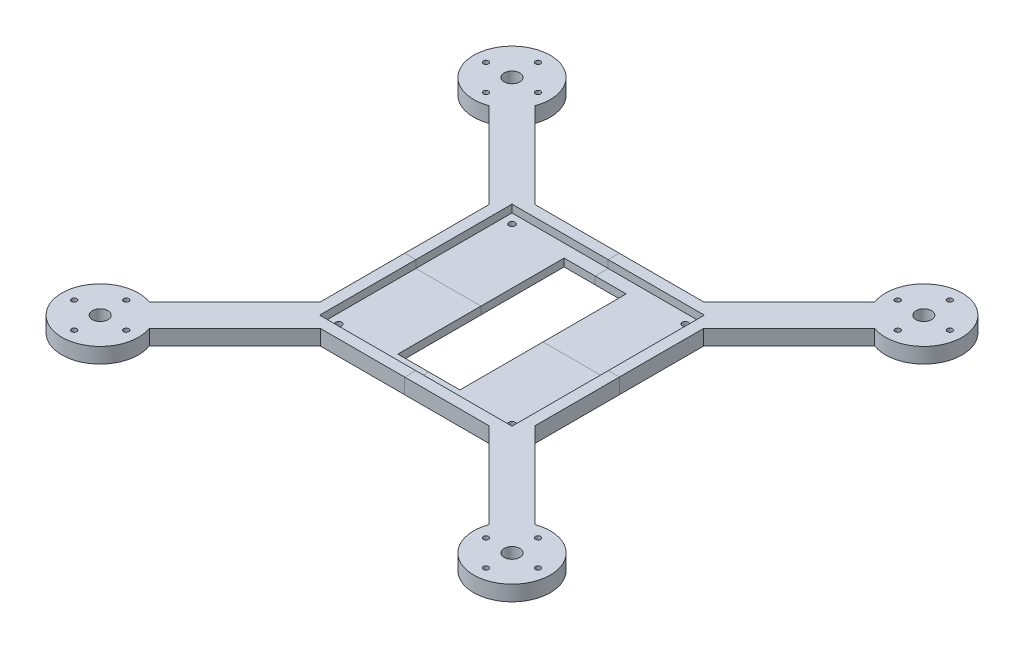
SolidWorks part; units mm, degrees
ref_plane "정면" through (0, 0, 0) normal (0, 0, 1) x (1, 0, 0)
ref_plane "윗면" through (0, 0, 0) normal (0, 1, 0) x (1, 0, 0)
ref_plane "우측면" through (0, 0, 0) normal (1, 0, 0) x (0, 0, -1)
sketch "스케치1" plane through (0, 0, 0) normal (0, 1, 0) x (1, 0, 0)
  line L0 (55, 70) -> (110.8425, 125.8425)
  line L1 (-55, 70) -> (55, 70)
  line L2 (-70, 55) -> (-70, -55)
  line L3 (-55, -70) -> (55, -70)
  line L4 (70, 55) -> (70, -55)
  line L5 (-60.2755, 60.2755) -> (60.2245, -60.2245) construction
  line L6 (-77.3477, -77.3477) -> (43.1523, 43.1523) construction
  line L7 (-20.25, 54.25) -> (20.25, 54.25)
  line L8 (-20.25, 54.25) -> (-20.25, -54.25)
  line L9 (-20.25, -54.25) -> (20.25, -54.25)
  line L10 (20.25, 54.25) -> (20.25, -54.25)
  line L11 (-20.25, 54.25) -> (20.25, -54.25) construction
  line L12 (-20.25, -54.25) -> (20.25, 54.25) construction
  line L13 (70, 55) -> (125.8425, 110.8425)
  line L14 (109.3503, 134.3503) -> (159.3503, 134.3503) construction
  line L15 (134.3503, 159.3503) -> (134.3503, 109.3503) construction
  line L16 (152.028, 116.6726) -> (116.6726, 152.028) construction
  line L17 (70, -55) -> (125.8425, -110.8425)
  line L18 (55, -70) -> (110.8425, -125.8425)
  line L19 (134.3503, -109.3503) -> (134.3503, -159.3503) construction
  line L20 (159.3503, -134.3503) -> (109.3503, -134.3503) construction
  line L21 (116.6726, -152.028) -> (152.028, -116.6726) construction
  line L22 (-55, -70) -> (-110.8425, -125.8425)
  line L23 (-70, -55) -> (-125.8425, -110.8425)
  line L24 (-109.3503, -134.3503) -> (-159.3503, -134.3503) construction
  line L25 (-134.3503, -159.3503) -> (-134.3503, -109.3503) construction
  line L26 (-152.028, -116.6726) -> (-116.6726, -152.028) construction
  line L27 (-70, 55) -> (-125.8425, 110.8425)
  line L28 (-55, 70) -> (-110.8425, 125.8425)
  line L29 (-134.3503, 109.3503) -> (-134.3503, 159.3503) construction
  line L30 (-159.3503, 134.3503) -> (-109.3503, 134.3503) construction
  line L31 (-116.6726, 152.028) -> (-152.028, 116.6726) construction
  line L32 (55, 70) -> (70, 70) construction
  line L33 (70, 70) -> (70, 55) construction
  line L34 (55, -70) -> (70, -70) construction
  line L35 (70, -55) -> (70, -70) construction
  line L36 (-70, -70) -> (-55, -70) construction
  line L37 (-70, -55) -> (-70, -70) construction
  line L38 (-70, 70) -> (-70, 55) construction
  line L39 (-70, 70) -> (-55, 70) construction
  line L45 (-56.5, 56.5) -> (56.5, -56.5) construction
  line L46 (-56.5, -56.5) -> (56.5, 56.5) construction
  circle A0 centre (-56.5, -56.5) radius 2
  circle A1 centre (56.5, -56.5) radius 2
  circle A2 centre (56.5, 56.5) radius 2
  circle A3 centre (-56.5, 56.5) radius 2
  arc A4 (125.8425, 110.8425) -> (110.8425, 125.8425) centre (134.3503, 134.3503) ccw
  arc A5 (110.8425, 125.8425) -> (116.6726, 116.6726) centre (134.3503, 134.3503) ccw construction
  arc A6 (116.6726, 116.6726) -> (125.8425, 110.8425) centre (134.3503, 134.3503) ccw construction
  circle A11 centre (134.3503, 117.3503) radius 1.7
  circle A12 centre (117.3503, 134.3503) radius 1.7
  circle A13 centre (151.3503, 134.3503) radius 1.7
  circle A14 centre (134.3503, 151.3503) radius 1.7
  circle A15 centre (134.3503, 134.3503) radius 5.1
  arc A16 (110.8425, -125.8425) -> (125.8425, -110.8425) centre (134.3503, -134.3503) ccw
  circle A17 centre (117.3503, -134.3503) radius 1.7
  circle A18 centre (134.3503, -117.3503) radius 1.7
  circle A19 centre (134.3503, -151.3503) radius 1.7
  circle A20 centre (151.3503, -134.3503) radius 1.7
  circle A21 centre (134.3503, -134.3503) radius 5.1
  arc A22 (125.8425, -110.8425) -> (116.6726, -116.6726) centre (134.3503, -134.3503) ccw construction
  arc A23 (116.6726, -116.6726) -> (110.8425, -125.8425) centre (134.3503, -134.3503) ccw construction
  arc A24 (-125.8425, -110.8425) -> (-110.8425, -125.8425) centre (-134.3503, -134.3503) ccw
  circle A25 centre (-134.3503, -117.3503) radius 1.7
  circle A26 centre (-117.3503, -134.3503) radius 1.7
  circle A27 centre (-151.3503, -134.3503) radius 1.7
  circle A28 centre (-134.3503, -151.3503) radius 1.7
  circle A29 centre (-134.3503, -134.3503) radius 5.1
  arc A30 (-110.8425, -125.8425) -> (-116.6726, -116.6726) centre (-134.3503, -134.3503) ccw construction
  arc A31 (-116.6726, -116.6726) -> (-125.8425, -110.8425) centre (-134.3503, -134.3503) ccw construction
  arc A32 (-110.8425, 125.8425) -> (-125.8425, 110.8425) centre (-134.3503, 134.3503) ccw
  circle A33 centre (-117.3503, 134.3503) radius 1.7
  circle A34 centre (-134.3503, 117.3503) radius 1.7
  circle A35 centre (-134.3503, 151.3503) radius 1.7
  circle A36 centre (-151.3503, 134.3503) radius 1.7
  circle A37 centre (-134.3503, 134.3503) radius 5.1
  arc A38 (-125.8425, 110.8425) -> (-116.6726, 116.6726) centre (-134.3503, 134.3503) ccw construction
  arc A39 (-116.6726, 116.6726) -> (-110.8425, 125.8425) centre (-134.3503, 134.3503) ccw construction
  point P0 (0, 0)
  point P6 (0, 0)
  point P28 (0, 54.25)
  point P32 (134.3503, 134.3503)
  point P38 (134.3503, 134.3503)
  point P48 (0, 0)
  point P57 (134.3503, -134.3503)
  point P63 (134.3503, -134.3503)
  point P80 (-134.3503, -134.3503)
  point P86 (-134.3503, -134.3503)
  point P103 (-134.3503, 134.3503)
  point P109 (-134.3503, 134.3503)
  dimension "D5" = 4
  dimension "D13" = 50
  dimension "D14" = 3.4
  dimension "D15" = 17
  dimension "D16" = 34
  dimension "D19" = 10.2
  dimension "D1" = 140
  dimension "D2" = 140
  dimension "D3" = 108.5
  dimension "D4" = 40.5
  dimension "D6" = 56.5
  dimension "D10" = 15
  dimension "D11" = 15
  dimension "D12" = 190
  dimension "D17" = 17
  dimension "D18" = 34
  dimension "D20" = 4
extrude "보스-돌출1" add sketch "스케치1" against normal blind 10
sketch "스케치4" plane through (0, 0, 0) normal (0, 1, 0) x (1, 0, 0)
  line L1 (-62.75, 62.75) -> (62.75, 62.75)
  line L2 (-62.75, 62.75) -> (-62.75, -62.75)
  line L3 (-62.75, -62.75) -> (62.75, -62.75)
  line L4 (62.75, 62.75) -> (62.75, -62.75)
  line L5 (-62.75, 62.75) -> (62.75, -62.75) construction
  line L6 (-62.75, -62.75) -> (62.75, 62.75) construction
  point P0 (0, 0)
  dimension "D1" = 125.5
  dimension "D2" = 125.5
extrude "컷-돌출1" cut sketch "스케치4" against normal blind 5
sketch "스케치5" plane through (0, 0, 0) normal (0, 1, 0) x (1, 0, 0)
  line L0 (0, 70) -> (0, -70)
  line L1 (-70, 0) -> (70, 0)
  line L2 (-55, -70) -> (55, -70) construction
  line L3 (70, -55) -> (70, 55) construction
  point P0 (70, 0)
  point P4 (0, 0)
  point P8 (0, 0)
sketch "스케치3" plane through (0, 0, 0) normal (0, 1, 0) x (1, 0, 0)
  line L0 (0, 0) -> (134.3503, 134.3503) construction
  line L1 (134.3503, 134.3503) -> (117.4358, 128.1939)
  line L2 (128.1939, 117.4358) -> (134.3503, 134.3503)
  circle A0 centre (134.3503, 134.3503) radius 13.9
  circle A1 centre (134.3503, 134.3503) radius 18
  arc A2 (117.4358, 128.1939) -> (128.1939, 117.4358) centre (134.3503, 134.3503) ccw
  arc M49 (125.8425, 110.8425) -> (110.8425, 125.8425) centre (134.3503, 134.3503) ccw
  dimension "D1" = 27.8
  dimension "D2" = 25
  dimension "D4" = 36
  dimension "D3" = 25
extrude "보스-돌출2" [suppressed] add sketch "스케치3" along normal blind 25 contours A1 L1 A0 L2 M49
ref_axis "기준축1" through (0, 26.25, 0) along (0, -1, 0)
pattern_circular "원형 패턴1" [suppressed] count 4 over 360 about axis through (0, 26.25, 0) along (0, -1, 0) of bodies 102
split "분할2" trim tools "스케치5" bodies to split 104 resulting bodies 109 110 111 112
